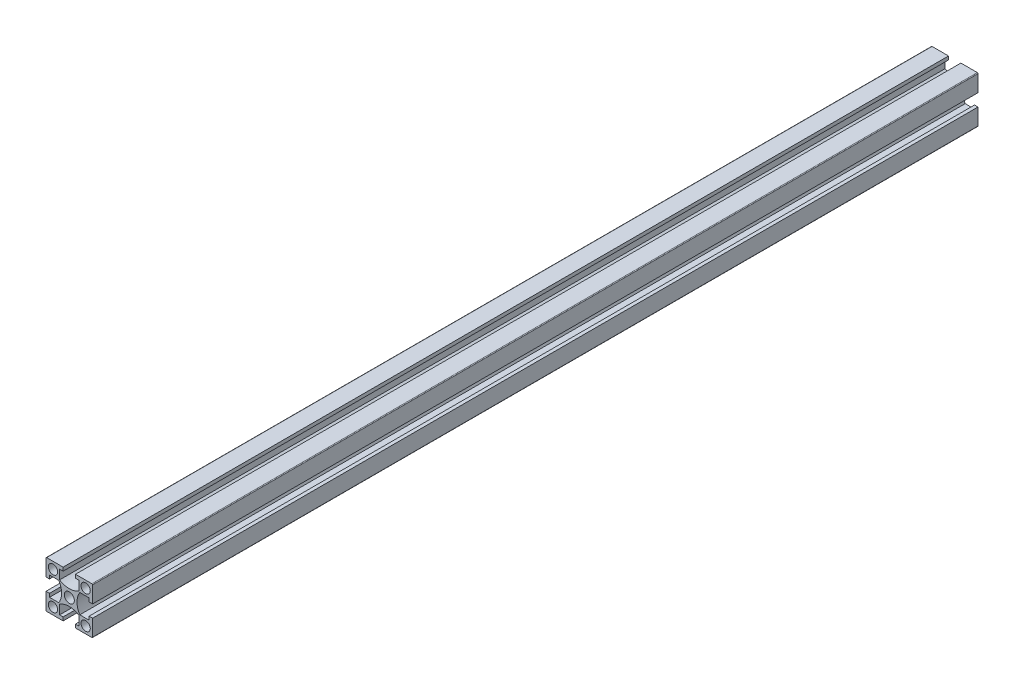
SolidWorks part; units mm, degrees
ref_plane "정면" through (0, 0, 0) normal (0, 0, 1) x (1, 0, 0)
ref_plane "윗면" through (0, 0, 0) normal (0, 1, 0) x (1, 0, 0)
ref_plane "우측면" through (0, 0, 0) normal (1, 0, 0) x (0, 0, -1)
sketch "스케치1" plane through (0, 0, 0) normal (0, 0, 1) x (1, 0, 0)
  line L0 (0, 32.0265) -> (0, -31.6588) construction
  line L1 (-10, 10) -> (-10, -10)
  line L2 (-10, 10) -> (10, 10)
  line L3 (-10, 2.65) -> (-8.5, 2.65)
  line L4 (13.6618, 0) -> (-11.6993, 0) construction
  line L5 (-8.5, 2.65) -> (-8.5, 4.15)
  line L6 (-8.5, 4.15) -> (-4.5032, 4.15)
  line L7 (-10, -2.65) -> (-8.5, -2.65)
  line L8 (-8.5, -2.65) -> (-8.5, -4.15)
  line L9 (-8.5, -4.15) -> (-4.5032, -4.15)
  line L10 (-10, -10) -> (10, -10)
  line L11 (10, 10) -> (10, -10)
  circle A0 centre (-7, 7) radius 2
  circle A1 centre (-7, -7) radius 2
  arc A2 (-4.5032, 4.15) -> (-4.5032, -4.15) centre (-11.0587, 0) cw
  circle A3 centre (0, 0) radius 2.15
  circle A4 centre (7, 7) radius 2
  circle A5 centre (7, -7) radius 2
  point P21 (-10, 0)
  point P23 (-3.3, 0)
  point P31 (0, -10)
  point P32 (0, 10)
  dimension "D3" = 4
  dimension "D9" = 6.7
  dimension "D10" = 4.3
  dimension "D11" = 7.7587
  dimension "D1" = 20
  dimension "D2" = 20
  dimension "D4" = 14
  dimension "D5" = 14
  dimension "D6" = 5.3
  dimension "D7" = 8.3
  dimension "D8" = 1.5
extrude "보스-돌출1" add sketch "스케치1" along normal blind 380 contours A0 | A4 | A3 | A5 | A1 | A2 L6 L5 L3 L1 L7 L8 L9 | L2 L11 L10 L1 region at (-6.6069, 0, 0) region at (-7, 7, 0) region at (-7, -7, 0) region at (0, 0, 0) region at (7, 7, 0) region at (7, -7, 0)
extrude "컷-돌출1" cut sketch "스케치1<3>" along normal up to next contours A2 L6 L5 L3 L1 L7 L8 L9 region at (-6.6069, 0, 0)
sketch "스케치1<3>" plane through (0, 0, 0) normal (0, 0, 1) x (1, 0, 0) same geometry as "스케치1"
pattern_circular "원형 패턴1" count 4 over 360 about axis through (0, 0, 380) along (0, 0, -1) of "컷-돌출1" reverse direction yes
fillet "필렛1" radius 0.3 4 edges at (10, -10, 190) (-10, -10, 190) (-10, 10, 190) (10, 10, 190)
